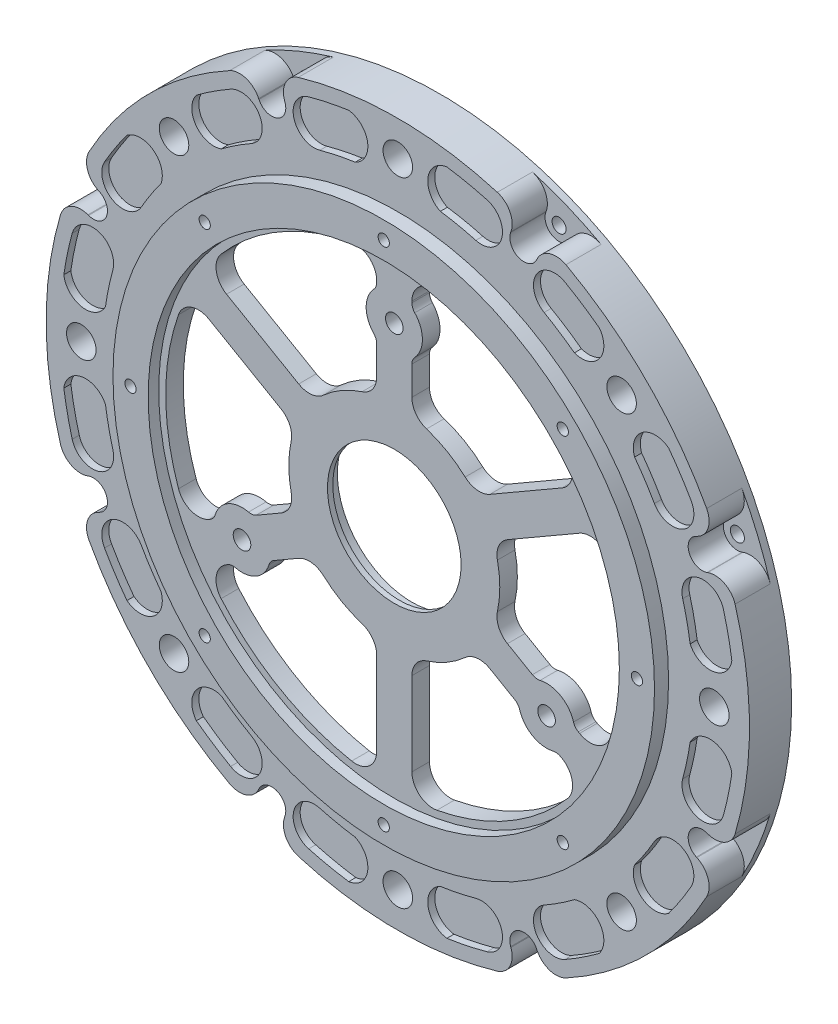
SolidWorks part; units mm, degrees
material "6061 Alloy"
ref_plane "Front Plane" through (0, 0, 0) normal (0, 0, 1) x (1, 0, 0)
ref_plane "Top Plane" through (0, 0, 0) normal (0, 1, 0) x (1, 0, 0)
ref_plane "Right Plane" through (0, 0, 0) normal (1, 0, 0) x (0, 0, -1)
sketch "Sketch1" plane through (0, 0, 0) normal (0, 0, 1) x (1, 0, 0)
  line L0 (0, 0) -> (0, 55.0351) construction
  line L1 (26.3498, 12.3263) -> (16.0929, 6.4045)
  line L2 (23.8498, 16.6564) -> (13.5929, 10.7346)
  line L3 (2.5, 28.9828) -> (2.5, 28.7749)
  line L4 (-2.5, 28.9828) -> (-2.5, 28.7749)
  line L5 (23.8498, -16.6564) -> (23.6698, -16.5525)
  line L6 (26.3498, -12.3263) -> (26.1698, -12.2224)
  line L7 (-2.5, -28.9828) -> (-2.5, -17.1391)
  line L8 (2.5, -28.9828) -> (2.5, -17.1391)
  line L9 (-26.3498, -12.3263) -> (-26.1698, -12.2224)
  line L10 (-23.8498, -16.6564) -> (-23.6698, -16.5525)
  line L11 (-23.8498, 16.6564) -> (-13.5929, 10.7346)
  line L12 (-26.3498, 12.3263) -> (-16.0929, 6.4045)
  line L13 (2.5, 21.2251) -> (2.5, 17.1391)
  line L14 (-2.5, 21.2251) -> (-2.5, 17.1391)
  line L15 (19.6315, -8.4475) -> (16.0929, -6.4045)
  line L16 (17.1315, -12.7776) -> (13.5929, -10.7346)
  line L17 (-17.1315, -12.7776) -> (-13.5929, -10.7346)
  line L18 (-19.6315, -8.4475) -> (-16.0929, -6.4045)
  circle A0 centre (0, 0) radius 50
  arc A3 (-6.0593, 31.9302) -> (-24.6227, 21.2126) centre (0, 0) ccw
  arc A4 (-4.5833, 14.2826) -> (-10.0774, 11.1106) centre (0, 0) ccw
  arc A5 (-6.0593, 31.9302) -> (-2.5, 28.9828) centre (-5.5, 28.9828) cw
  arc A6 (-4.5833, 14.2826) -> (-2.5, 17.1391) centre (-5.5, 17.1391) ccw
  arc A7 (2.5, 17.1391) -> (4.5833, 14.2826) centre (5.5, 17.1391) ccw
  arc A8 (6.0593, 31.9302) -> (2.5, 28.9828) centre (5.5, 28.9828) ccw
  arc A9 (30.682, 10.7175) -> (26.3498, 12.3263) centre (27.8498, 9.7282) ccw
  arc A10 (16.0929, 6.4045) -> (14.6608, 3.172) centre (17.5929, 3.8064) ccw
  arc A11 (10.0774, 11.1106) -> (13.5929, 10.7346) centre (12.0929, 13.3327) ccw
  arc A12 (24.6227, 21.2126) -> (23.8498, 16.6564) centre (22.3498, 19.2545) cw
  arc A13 (24.6227, -21.2126) -> (23.8498, -16.6564) centre (22.3498, -19.2545) ccw
  arc A14 (13.5929, -10.7346) -> (10.0774, -11.1106) centre (12.0929, -13.3327) ccw
  arc A15 (14.6608, -3.172) -> (16.0929, -6.4045) centre (17.5929, -3.8064) ccw
  arc A16 (30.682, -10.7175) -> (26.3498, -12.3263) centre (27.8498, -9.7282) cw
  arc A17 (-6.0593, -31.9302) -> (-2.5, -28.9828) centre (-5.5, -28.9828) ccw
  arc A18 (-2.5, -17.1391) -> (-4.5833, -14.2826) centre (-5.5, -17.1391) ccw
  arc A19 (4.5833, -14.2826) -> (2.5, -17.1391) centre (5.5, -17.1391) ccw
  arc A20 (6.0593, -31.9302) -> (2.5, -28.9828) centre (5.5, -28.9828) cw
  arc A21 (-30.682, -10.7175) -> (-26.3498, -12.3263) centre (-27.8498, -9.7282) ccw
  arc A22 (-16.0929, -6.4045) -> (-14.6608, -3.172) centre (-17.5929, -3.8064) ccw
  arc A23 (-10.0774, -11.1106) -> (-13.5929, -10.7346) centre (-12.0929, -13.3327) ccw
  arc A24 (-24.6227, -21.2126) -> (-23.8498, -16.6564) centre (-22.3498, -19.2545) cw
  arc A25 (-24.6227, 21.2126) -> (-23.8498, 16.6564) centre (-22.3498, 19.2545) ccw
  arc A26 (-13.5929, 10.7346) -> (-10.0774, 11.1106) centre (-12.0929, 13.3327) ccw
  arc A27 (-14.6608, 3.172) -> (-16.0929, 6.4045) centre (-17.5929, 3.8064) ccw
  arc A28 (-30.682, 10.7175) -> (-26.3498, 12.3263) centre (-27.8498, 9.7282) cw
  arc A29 (-30.682, 10.7175) -> (-30.682, -10.7175) centre (0, 0) ccw
  arc A30 (-24.6227, -21.2126) -> (-6.0593, -31.9302) centre (0, 0) ccw
  arc A31 (6.0593, -31.9302) -> (24.6227, -21.2126) centre (0, 0) ccw
  arc A32 (30.682, -10.7175) -> (30.682, 10.7175) centre (0, 0) ccw
  arc A33 (24.6227, 21.2126) -> (6.0593, 31.9302) centre (0, 0) ccw
  arc A34 (-14.6608, 3.172) -> (-14.6608, -3.172) centre (0, 0) ccw
  arc A35 (-10.0774, -11.1106) -> (-4.5833, -14.2826) centre (0, 0) ccw
  arc A36 (4.5833, -14.2826) -> (10.0774, -11.1106) centre (0, 0) ccw
  arc A37 (14.6608, -3.172) -> (14.6608, 3.172) centre (0, 0) ccw
  arc A38 (10.0774, 11.1106) -> (4.5833, 14.2826) centre (0, 0) ccw
  circle A39 centre (0, 0) radius 10.6
  circle A40 centre (0, 0) radius 25 construction
  arc A41 (2.9091, 22.2546) -> (2.9091, 27.7454) centre (0, 25) ccw
  arc A42 (-2.9091, 27.7454) -> (-2.9091, 22.2546) centre (0, 25) ccw
  arc A43 (17.8185, -13.6466) -> (22.5737, -16.392) centre (21.6506, -12.5) ccw
  arc A44 (25.4828, -11.3534) -> (20.7276, -8.608) centre (21.6506, -12.5) ccw
  arc A45 (-20.7276, -8.608) -> (-25.4828, -11.3534) centre (-21.6506, -12.5) ccw
  arc A46 (-22.5737, -16.392) -> (-17.8185, -13.6466) centre (-21.6506, -12.5) ccw
  arc A47 (17.8185, -13.6466) -> (17.1315, -12.7776) centre (16.3815, -14.0766) ccw
  arc A48 (19.6315, -8.4475) -> (20.7276, -8.608) centre (20.3815, -7.1484) ccw
  arc A49 (25.4828, -11.3534) -> (26.1698, -12.2224) centre (26.9198, -10.9234) ccw
  arc A50 (22.5737, -16.392) -> (23.6698, -16.5525) centre (22.9198, -17.8516) cw
  arc A51 (-25.4828, -11.3534) -> (-26.1698, -12.2224) centre (-26.9198, -10.9234) cw
  arc A52 (-22.5737, -16.392) -> (-23.6698, -16.5525) centre (-22.9198, -17.8516) ccw
  arc A53 (-17.8185, -13.6466) -> (-17.1315, -12.7776) centre (-16.3815, -14.0766) cw
  arc A54 (-19.6315, -8.4475) -> (-20.7276, -8.608) centre (-20.3815, -7.1484) cw
  arc A55 (2.5, 21.2251) -> (2.9091, 22.2546) centre (4, 21.2251) cw
  arc A56 (2.9091, 27.7454) -> (2.5, 28.7749) centre (4, 28.7749) cw
  arc A57 (-2.9091, 22.2546) -> (-2.5, 21.2251) centre (-4, 21.2251) cw
  arc A58 (-2.5, 28.7749) -> (-2.9091, 27.7454) centre (-4, 28.7749) cw
  point P82 (0, 0)
  point P97 (0, 0)
  point P119 (-2.5, 28.1225)
  dimension "D1" = 100
  dimension "D2" = 21.2
  dimension "D5" = 50
  dimension "D6" = 65
  dimension "D7" = 30
  dimension "D8" = 3
  dimension "D10" = 8
  dimension "D12" = 1.5
  dimension "D3" = 2.5
  dimension "D4" = 2.5
  dimension "D9" = 6
  dimension "D11" = 3
extrude "Boss-Extrude1" add sketch "Sketch1" along normal blind 9
sketch "Sketch2" plane through (0, 0, 0) normal (0, 0, 1) x (1, 0, 0)
  line L17 (-3.8971, 42.75) -> (-5.0043, 44.6677)
  line L56 (19.6941, 40.983) -> (19.9564, 41.1843)
  line L57 (3.8971, 42.75) -> (5.0043, 44.6677)
  line L58 (40.983, 19.6941) -> (41.1843, 19.9564)
  line L59 (27.4731, 32.9845) -> (28.0463, 35.1234)
  line L60 (42.9052, 15.0535) -> (43.233, 15.0104)
  line L61 (32.9845, 27.4731) -> (35.1234, 28.0463)
  line L62 (42.9052, -15.0535) -> (43.233, -15.0104)
  line L63 (42.75, 3.8971) -> (44.6677, 5.0043)
  line L64 (40.983, -19.6941) -> (41.1843, -19.9564)
  line L65 (42.75, -3.8971) -> (44.6677, -5.0043)
  line L66 (19.6941, -40.983) -> (19.9564, -41.1843)
  line L67 (32.9845, -27.4731) -> (35.1234, -28.0463)
  line L68 (15.0535, -42.9052) -> (15.0104, -43.233)
  line L69 (27.4731, -32.9845) -> (28.0463, -35.1234)
  line L70 (-15.0535, -42.9052) -> (-15.0104, -43.233)
  line L71 (3.8971, -42.75) -> (5.0043, -44.6677)
  line L72 (-19.6941, -40.983) -> (-19.9564, -41.1843)
  line L73 (-3.8971, -42.75) -> (-5.0043, -44.6677)
  line L74 (-40.983, -19.6941) -> (-41.1843, -19.9564)
  line L75 (-27.4731, -32.9845) -> (-28.0463, -35.1234)
  line L76 (0, 0) -> (0, 52.4279) construction
  line L77 (0, 0) -> (17.9287, 43.2838) construction
  line L78 (-42.9052, -15.0535) -> (-43.233, -15.0104)
  line L79 (-32.9845, -27.4731) -> (-35.1234, -28.0463)
  line L80 (-42.9052, 15.0535) -> (-43.233, 15.0104)
  line L81 (-42.75, -3.8971) -> (-44.6677, -5.0043)
  line L82 (-40.983, 19.6941) -> (-41.1843, 19.9564)
  line L83 (-42.75, 3.8971) -> (-44.6677, 5.0043)
  line L84 (-19.6941, 40.983) -> (-19.9564, 41.1843)
  line L85 (-32.9845, 27.4731) -> (-35.1234, 28.0463)
  line L86 (-15.0535, 42.9052) -> (-15.0104, 43.233)
  line L87 (-27.4731, 32.9845) -> (-28.0463, 35.1234)
  line L88 (15.0535, 42.9052) -> (15.0104, 43.233)
  arc A46 (-3.8971, 42.75) -> (3.8971, 42.75) centre (0, 45) ccw
  arc A110 (15.0535, 42.9052) -> (19.6941, 40.983) centre (17.9287, 43.2838) ccw
  circle A111 centre (0, 0) radius 46.85 construction
  circle A112 centre (0, 0) radius 45 construction
  arc A114 (19.9564, 41.1843) -> (23.2512, 41.4202) centre (21.7827, 38.8042) cw
  arc A115 (5.0043, 44.6677) -> (9.2471, 46.5912) centre (8.4684, 42.6677) cw
  arc A116 (15.0104, 43.233) -> (12.8475, 45.7296) centre (12.036, 42.8414) ccw
  arc A117 (-5.0043, 44.6677) -> (-9.2471, 46.5912) centre (-8.4684, 42.6677) ccw
  arc A118 (27.4731, 32.9845) -> (32.9845, 27.4731) centre (31.8198, 31.8198) ccw
  arc A119 (40.983, 19.6941) -> (42.9052, 15.0535) centre (43.2838, 17.9287) ccw
  arc A120 (43.233, 15.0104) -> (45.7296, 12.8475) centre (42.8414, 12.036) cw
  arc A121 (35.1234, 28.0463) -> (39.4837, 26.4063) centre (36.1587, 24.1826) cw
  arc A122 (41.1843, 19.9564) -> (41.4202, 23.2512) centre (38.8042, 21.7827) ccw
  arc A123 (28.0463, 35.1234) -> (26.4063, 39.4837) centre (24.1826, 36.1587) ccw
  arc A124 (42.75, 3.8971) -> (42.75, -3.8971) centre (45, 0) ccw
  arc A125 (42.9052, -15.0535) -> (40.983, -19.6941) centre (43.2838, -17.9287) ccw
  arc A126 (41.1843, -19.9564) -> (41.4202, -23.2512) centre (38.8042, -21.7827) cw
  arc A127 (44.6677, -5.0043) -> (46.5912, -9.2471) centre (42.6677, -8.4684) cw
  arc A128 (43.233, -15.0104) -> (45.7296, -12.8475) centre (42.8414, -12.036) ccw
  arc A129 (44.6677, 5.0043) -> (46.5912, 9.2471) centre (42.6677, 8.4684) ccw
  arc A130 (32.9845, -27.4731) -> (27.4731, -32.9845) centre (31.8198, -31.8198) ccw
  arc A131 (19.6941, -40.983) -> (15.0535, -42.9052) centre (17.9287, -43.2838) ccw
  arc A132 (15.0104, -43.233) -> (12.8475, -45.7296) centre (12.036, -42.8414) cw
  arc A133 (28.0463, -35.1234) -> (26.4063, -39.4837) centre (24.1826, -36.1587) cw
  arc A134 (19.9564, -41.1843) -> (23.2512, -41.4202) centre (21.7827, -38.8042) ccw
  arc A135 (35.1234, -28.0463) -> (39.4837, -26.4063) centre (36.1587, -24.1826) ccw
  arc A136 (3.8971, -42.75) -> (-3.8971, -42.75) centre (0, -45) ccw
  arc A137 (-15.0535, -42.9052) -> (-19.6941, -40.983) centre (-17.9287, -43.2838) ccw
  arc A138 (-19.9564, -41.1843) -> (-23.2512, -41.4202) centre (-21.7827, -38.8042) cw
  arc A139 (-5.0043, -44.6677) -> (-9.2471, -46.5912) centre (-8.4684, -42.6677) cw
  arc A140 (-15.0104, -43.233) -> (-12.8475, -45.7296) centre (-12.036, -42.8414) ccw
  arc A141 (5.0043, -44.6677) -> (9.2471, -46.5912) centre (8.4684, -42.6677) ccw
  arc A142 (-27.4731, -32.9845) -> (-32.9845, -27.4731) centre (-31.8198, -31.8198) ccw
  arc A143 (-40.983, -19.6941) -> (-42.9052, -15.0535) centre (-43.2838, -17.9287) ccw
  arc A144 (-43.233, -15.0104) -> (-45.7296, -12.8475) centre (-42.8414, -12.036) cw
  arc A145 (-35.1234, -28.0463) -> (-39.4837, -26.4063) centre (-36.1587, -24.1826) cw
  arc A146 (-41.1843, -19.9564) -> (-41.4202, -23.2512) centre (-38.8042, -21.7827) ccw
  arc A147 (-28.0463, -35.1234) -> (-26.4063, -39.4837) centre (-24.1826, -36.1587) ccw
  arc A148 (-42.75, -3.8971) -> (-42.75, 3.8971) centre (-45, 0) ccw
  arc A149 (-42.9052, 15.0535) -> (-40.983, 19.6941) centre (-43.2838, 17.9287) ccw
  arc A150 (-41.1843, 19.9564) -> (-41.4202, 23.2512) centre (-38.8042, 21.7827) cw
  arc A151 (-44.6677, 5.0043) -> (-46.5912, 9.2471) centre (-42.6677, 8.4684) cw
  arc A152 (-43.233, 15.0104) -> (-45.7296, 12.8475) centre (-42.8414, 12.036) ccw
  arc A153 (-44.6677, -5.0043) -> (-46.5912, -9.2471) centre (-42.6677, -8.4684) ccw
  arc A154 (-32.9845, 27.4731) -> (-27.4731, 32.9845) centre (-31.8198, 31.8198) ccw
  arc A155 (-19.6941, 40.983) -> (-15.0535, 42.9052) centre (-17.9287, 43.2838) ccw
  arc A156 (-15.0104, 43.233) -> (-12.8475, 45.7296) centre (-12.036, 42.8414) cw
  arc A157 (-28.0463, 35.1234) -> (-26.4063, 39.4837) centre (-24.1826, 36.1587) cw
  arc A158 (-19.9564, 41.1843) -> (-23.2512, 41.4202) centre (-21.7827, 38.8042) ccw
  arc A159 (-35.1234, 28.0463) -> (-39.4837, 26.4063) centre (-36.1587, 24.1826) ccw
  arc A160 (26.4063, 39.4837) -> (23.2512, 41.4202) centre (0, 0) ccw
  arc A161 (12.8475, 45.7296) -> (9.2471, 46.5912) centre (0, 0) ccw
  arc A162 (-9.2471, 46.5912) -> (-12.8475, 45.7296) centre (0, 0) ccw
  arc A163 (-23.2512, 41.4202) -> (-26.4063, 39.4837) centre (0, 0) ccw
  arc A164 (-39.4837, 26.4063) -> (-41.4202, 23.2512) centre (0, 0) ccw
  arc A165 (-45.7296, 12.8475) -> (-46.5912, 9.2471) centre (0, 0) ccw
  arc A166 (-46.5912, -9.2471) -> (-45.7296, -12.8475) centre (0, 0) ccw
  arc A167 (-41.4202, -23.2512) -> (-39.4837, -26.4063) centre (0, 0) ccw
  arc A168 (-26.4063, -39.4837) -> (-23.2512, -41.4202) centre (0, 0) ccw
  arc A169 (-12.8475, -45.7296) -> (-9.2471, -46.5912) centre (0, 0) ccw
  arc A170 (9.2471, -46.5912) -> (12.8475, -45.7296) centre (0, 0) ccw
  arc A171 (23.2512, -41.4202) -> (26.4063, -39.4837) centre (0, 0) ccw
  arc A172 (39.4837, -26.4063) -> (41.4202, -23.2512) centre (0, 0) ccw
  arc A173 (45.7296, -12.8475) -> (46.5912, -9.2471) centre (0, 0) ccw
  arc A174 (46.5912, 9.2471) -> (45.7296, 12.8475) centre (0, 0) ccw
  arc A175 (41.4202, 23.2512) -> (39.4837, 26.4063) centre (0, 0) ccw
  point P159 (0, 0)
  dimension "D1" = 2.9
  dimension "D2" = 93.7
  dimension "D3" = 90
  dimension "D4" = 22.5
  dimension "D5" = 95
  dimension "D6" = 9
  dimension "D9" = 3
  dimension "D10" = 4
  dimension "D7" = 8
extrude "Cut-Extrude2" cut sketch "Sketch2" along normal blind 5 from surface starting at face at (-14.1218, -17.8169, 0)
sketch "Sketch3" plane through (0, 0, 0) normal (0, 0, 1) x (1, 0, 0)
  circle A0 centre (0, 0) radius 50
  circle A1 centre (0, 0) radius 48.4
  dimension "D1" = 100
  dimension "D2" = 96.8
extrude "Cut-Extrude3" cut sketch "Sketch3" along normal blind 1 from surface starting at face at (50, 0, 0)
sketch "Sketch4" plane through (0, 0, 0) normal (0, 0, 1) x (1, 0, 0)
  line L0 (0, 0) -> (0, 58.9666) construction
  line L1 (0, 0) -> (-11.6574, 58.6055) construction
  circle A0 centre (0, 0) radius 45 construction
  arc A3 (-12.6755, 46.2961) -> (-11.0911, 40.5091) centre (-11.8833, 43.4026) ccw
  arc A5 (-6.9776, 47.4901) -> (-12.6755, 46.2961) centre (0, 0) ccw
  arc A6 (-6.0511, 41.5618) -> (-11.0911, 40.5091) centre (0, 0) ccw
  arc A7 (-6.0511, 41.5618) -> (-6.9776, 47.4901) centre (-7.3833, 44.3902) ccw
  arc A8 (6.0511, 41.5618) -> (11.0911, 40.5091) centre (0, 0) cw
  arc A9 (6.0511, 41.5618) -> (6.9776, 47.4901) centre (7.3833, 44.3902) cw
  arc A10 (6.9776, 47.4901) -> (12.6755, 46.2961) centre (0, 0) cw
  arc A11 (12.6755, 46.2961) -> (11.0911, 40.5091) centre (11.8833, 43.4026) cw
  arc A12 (25.1099, 33.6674) -> (20.8017, 36.4868) centre (0, 0) ccw
  arc A13 (23.7733, 41.6993) -> (20.8017, 36.4868) centre (22.2875, 39.0931) ccw
  arc A14 (28.6467, 38.5145) -> (23.7733, 41.6993) centre (0, 0) ccw
  arc A15 (25.1099, 33.6674) -> (28.6467, 38.5145) centre (26.1678, 36.6094) ccw
  arc A16 (33.6674, 25.1099) -> (36.4868, 20.8017) centre (0, 0) cw
  arc A17 (33.6674, 25.1099) -> (38.5145, 28.6467) centre (36.6094, 26.1678) cw
  arc A18 (38.5145, 28.6467) -> (41.6993, 23.7733) centre (0, 0) cw
  arc A19 (41.6993, 23.7733) -> (36.4868, 20.8017) centre (39.0931, 22.2875) cw
  arc A20 (41.5618, 6.0511) -> (40.5091, 11.0911) centre (0, 0) ccw
  arc A21 (46.2961, 12.6755) -> (40.5091, 11.0911) centre (43.4026, 11.8833) ccw
  arc A22 (47.4901, 6.9776) -> (46.2961, 12.6755) centre (0, 0) ccw
  arc A23 (41.5618, 6.0511) -> (47.4901, 6.9776) centre (44.3902, 7.3833) ccw
  arc A24 (41.5618, -6.0511) -> (40.5091, -11.0911) centre (0, 0) cw
  arc A25 (41.5618, -6.0511) -> (47.4901, -6.9776) centre (44.3902, -7.3833) cw
  arc A26 (47.4901, -6.9776) -> (46.2961, -12.6755) centre (0, 0) cw
  arc A27 (46.2961, -12.6755) -> (40.5091, -11.0911) centre (43.4026, -11.8833) cw
  arc A28 (33.6674, -25.1099) -> (36.4868, -20.8017) centre (0, 0) ccw
  arc A29 (41.6993, -23.7733) -> (36.4868, -20.8017) centre (39.0931, -22.2875) ccw
  arc A30 (38.5145, -28.6467) -> (41.6993, -23.7733) centre (0, 0) ccw
  arc A31 (33.6674, -25.1099) -> (38.5145, -28.6467) centre (36.6094, -26.1678) ccw
  arc A32 (25.1099, -33.6674) -> (20.8017, -36.4868) centre (0, 0) cw
  arc A33 (25.1099, -33.6674) -> (28.6467, -38.5145) centre (26.1678, -36.6094) cw
  arc A34 (28.6467, -38.5145) -> (23.7733, -41.6993) centre (0, 0) cw
  arc A35 (23.7733, -41.6993) -> (20.8017, -36.4868) centre (22.2875, -39.0931) cw
  arc A36 (6.0511, -41.5618) -> (11.0911, -40.5091) centre (0, 0) ccw
  arc A37 (12.6755, -46.2961) -> (11.0911, -40.5091) centre (11.8833, -43.4026) ccw
  arc A38 (6.9776, -47.4901) -> (12.6755, -46.2961) centre (0, 0) ccw
  arc A39 (6.0511, -41.5618) -> (6.9776, -47.4901) centre (7.3833, -44.3902) ccw
  arc A40 (-6.0511, -41.5618) -> (-11.0911, -40.5091) centre (0, 0) cw
  arc A41 (-6.0511, -41.5618) -> (-6.9776, -47.4901) centre (-7.3833, -44.3902) cw
  arc A42 (-6.9776, -47.4901) -> (-12.6755, -46.2961) centre (0, 0) cw
  arc A43 (-12.6755, -46.2961) -> (-11.0911, -40.5091) centre (-11.8833, -43.4026) cw
  arc A44 (-25.1099, -33.6674) -> (-20.8017, -36.4868) centre (0, 0) ccw
  arc A45 (-23.7733, -41.6993) -> (-20.8017, -36.4868) centre (-22.2875, -39.0931) ccw
  arc A46 (-28.6467, -38.5145) -> (-23.7733, -41.6993) centre (0, 0) ccw
  arc A47 (-25.1099, -33.6674) -> (-28.6467, -38.5145) centre (-26.1678, -36.6094) ccw
  arc A48 (-33.6674, -25.1099) -> (-36.4868, -20.8017) centre (0, 0) cw
  arc A49 (-33.6674, -25.1099) -> (-38.5145, -28.6467) centre (-36.6094, -26.1678) cw
  arc A50 (-38.5145, -28.6467) -> (-41.6993, -23.7733) centre (0, 0) cw
  arc A51 (-41.6993, -23.7733) -> (-36.4868, -20.8017) centre (-39.0931, -22.2875) cw
  arc A52 (-41.5618, -6.0511) -> (-40.5091, -11.0911) centre (0, 0) ccw
  arc A53 (-46.2961, -12.6755) -> (-40.5091, -11.0911) centre (-43.4026, -11.8833) ccw
  arc A54 (-47.4901, -6.9776) -> (-46.2961, -12.6755) centre (0, 0) ccw
  arc A55 (-41.5618, -6.0511) -> (-47.4901, -6.9776) centre (-44.3902, -7.3833) ccw
  arc A56 (-41.5618, 6.0511) -> (-40.5091, 11.0911) centre (0, 0) cw
  arc A57 (-41.5618, 6.0511) -> (-47.4901, 6.9776) centre (-44.3902, 7.3833) cw
  arc A58 (-47.4901, 6.9776) -> (-46.2961, 12.6755) centre (0, 0) cw
  arc A59 (-46.2961, 12.6755) -> (-40.5091, 11.0911) centre (-43.4026, 11.8833) cw
  arc A60 (-33.6674, 25.1099) -> (-36.4868, 20.8017) centre (0, 0) ccw
  arc A61 (-41.6993, 23.7733) -> (-36.4868, 20.8017) centre (-39.0931, 22.2875) ccw
  arc A62 (-38.5145, 28.6467) -> (-41.6993, 23.7733) centre (0, 0) ccw
  arc A63 (-33.6674, 25.1099) -> (-38.5145, 28.6467) centre (-36.6094, 26.1678) ccw
  arc A64 (-25.1099, 33.6674) -> (-20.8017, 36.4868) centre (0, 0) cw
  arc A65 (-25.1099, 33.6674) -> (-28.6467, 38.5145) centre (-26.1678, 36.6094) cw
  arc A66 (-28.6467, 38.5145) -> (-23.7733, 41.6993) centre (0, 0) cw
  arc A67 (-23.7733, 41.6993) -> (-20.8017, 36.4868) centre (-22.2875, 39.0931) cw
  point P110 (0, 0)
  dimension "D2" = 90
  dimension "D5" = 6
  dimension "D6" = 8
  dimension "D8" = 96
  dimension "D9" = 84
  dimension "D1" = 11.25
  dimension "D7" = 4.5
extrude "Cut-Extrude4" cut sketch "Sketch4" against normal blind 3 from surface starting at face at (-8.369, 21.1383, 9)
sketch "Sketch5" plane through (0, 0, 0) normal (0, 0, 1) x (1, 0, 0)
  circle A0 centre (0, 0) radius 38.5
  circle A1 centre (0, 0) radius 33.5
  dimension "D1" = 67
  dimension "D2" = 77
sketch "Sketch6" plane through (0, 0, 0) normal (0, 0, 1) x (1, 0, 0)
  circle A0 centre (0, 0) radius 38.5
  circle A1 centre (0, 0) radius 50
  dimension "D1" = 100
  dimension "D2" = 77
extrude "Cut-Extrude5" cut sketch "Sketch6" against normal blind 2 from surface starting at face at (-8.369, 21.1383, 9)
extrude "Cut-Extrude6" cut sketch "Sketch5" against normal blind 1.5 from surface contours A1 region at (0, 0, 0) starting at face at (-22.4908, -3.3214, 9)
sketch "Sketch7" plane through (0, 0, 0) normal (0, 0, 1) x (1, 0, 0)
  circle A0 centre (0, 25) radius 1.5
  circle A2 centre (21.6506, -12.5) radius 1.5
  circle A3 centre (-21.6506, -12.5) radius 1.5
  circle A4 centre (0, 0) radius 36 construction
  circle A5 centre (0, 36) radius 1
  circle A6 centre (25.4558, 25.4558) radius 1
  circle A7 centre (36, 0) radius 1
  circle A8 centre (25.4558, -25.4558) radius 1
  circle A9 centre (0, -36) radius 1
  circle A10 centre (-25.4558, -25.4558) radius 1
  circle A11 centre (-36, 0) radius 1
  circle A12 centre (-25.4558, 25.4558) radius 1
  point P9 (0, 0)
  point P30 (0, 0)
  dimension "D1" = 3
  dimension "D3" = 72
  dimension "D4" = 2
  dimension "D2" = 3
  dimension "D5" = 8
sketch "Sketch16" plane through (0, 0, 0) normal (0, 0, 1) x (1, 0, 0)
  line L0 (0, 0) -> (0, 60.4181) construction
  circle A0 centre (0, 0) radius 45 construction
  circle A1 centre (0, 45) radius 2.5
  circle A2 centre (31.8198, 31.8198) radius 2.5
  circle A3 centre (45, 0) radius 2.5
  circle A4 centre (31.8198, -31.8198) radius 2.5
  circle A5 centre (0, -45) radius 2.5
  circle A6 centre (-31.8198, -31.8198) radius 2.5
  circle A7 centre (-45, 0) radius 2.5
  circle A8 centre (-31.8198, 31.8198) radius 2.5
  point P23 (0, 0)
  dimension "D1" = 90
  dimension "D2" = 5
  dimension "D3" = 8
sketch "Sketch22" plane through (0, 0, 0) normal (0, 0, 1) x (1, 0, 0)
  line L0 (0, 0) -> (-20.8165, 50.2555) construction
  line L1 (0, 0) -> (0, 52.0381) construction
  circle A0 centre (0, 0) radius 46.85 construction
  circle A1 centre (-17.9287, 43.2838) radius 1
  circle A3 centre (17.9287, 43.2838) radius 1
  circle A4 centre (43.2838, 17.9287) radius 1
  circle A5 centre (43.2838, -17.9287) radius 1
  circle A6 centre (17.9287, -43.2838) radius 1
  circle A7 centre (-17.9287, -43.2838) radius 1
  circle A8 centre (-43.2838, -17.9287) radius 1
  circle A9 centre (-43.2838, 17.9287) radius 1
  point P23 (0, 0)
  dimension "D1" = 93.7
  dimension "D3" = 2
  dimension "D4" = 8
  dimension "D2" = 22.5
extrude "Cut-Extrude9" cut sketch "Sketch22" against normal through all from surface contours A1 | A3 | A4 | A5 | A6 | A7 | A8 | A9 starting at face at (-9.3758, 43.8939, 7)
sketch "Sketch23" plane through (0, 0, 0) normal (0, 0, 1) x (1, 0, 0)
  line L0 (0, 0) -> (-20.6937, 49.959) construction
  line L1 (0, 0) -> (0, 52.176) construction
  line L4 (-19.7428, 42.4416) -> (-19.7821, 42.5262)
  line L5 (-16.0505, 43.971) -> (-16.0826, 44.0586)
  line L6 (16.0505, 43.971) -> (16.0826, 44.0586)
  line L7 (19.7428, 42.4416) -> (19.7821, 42.5262)
  line L8 (42.4416, 19.7428) -> (42.5262, 19.7821)
  line L9 (43.971, 16.0505) -> (44.0586, 16.0826)
  line L10 (43.971, -16.0505) -> (44.0586, -16.0826)
  line L11 (42.4416, -19.7428) -> (42.5262, -19.7821)
  line L12 (19.7428, -42.4416) -> (19.7821, -42.5262)
  line L13 (16.0505, -43.971) -> (16.0826, -44.0586)
  line L14 (-16.0505, -43.971) -> (-16.0826, -44.0586)
  line L15 (-19.7428, -42.4416) -> (-19.7821, -42.5262)
  line L16 (-42.4416, -19.7428) -> (-42.5262, -19.7821)
  line L17 (-43.971, -16.0505) -> (-44.0586, -16.0826)
  line L18 (-43.971, 16.0505) -> (-44.0586, 16.0826)
  line L19 (-42.4416, 19.7428) -> (-42.5262, 19.7821)
  circle A0 centre (0, 0) radius 46.85 construction
  arc A1 (-19.7428, 42.4416) -> (-16.0505, 43.971) centre (-17.9287, 43.2838) ccw
  arc A8 (-14.148, 47.9566) -> (-16.0826, 44.0586) centre (-13.2652, 45.0894) ccw
  arc A9 (-19.7821, 42.5262) -> (-23.9063, 43.9146) centre (-22.5031, 41.2629) ccw
  arc A10 (-14.148, 47.9566) -> (-23.9063, 43.9146) centre (0, 0) ccw
  arc A11 (16.0505, 43.971) -> (19.7428, 42.4416) centre (17.9287, 43.2838) ccw
  arc A12 (23.9063, 43.9146) -> (19.7821, 42.5262) centre (22.5031, 41.2629) ccw
  arc A13 (16.0826, 44.0586) -> (14.148, 47.9566) centre (13.2652, 45.0894) ccw
  arc A14 (23.9063, 43.9146) -> (14.148, 47.9566) centre (0, 0) ccw
  arc A15 (42.4416, 19.7428) -> (43.971, 16.0505) centre (43.2838, 17.9287) ccw
  arc A16 (47.9566, 14.148) -> (44.0586, 16.0826) centre (45.0894, 13.2652) ccw
  arc A17 (42.5262, 19.7821) -> (43.9146, 23.9063) centre (41.2629, 22.5031) ccw
  arc A18 (47.9566, 14.148) -> (43.9146, 23.9063) centre (0, 0) ccw
  arc A19 (43.971, -16.0505) -> (42.4416, -19.7428) centre (43.2838, -17.9287) ccw
  arc A20 (43.9146, -23.9063) -> (42.5262, -19.7821) centre (41.2629, -22.5031) ccw
  arc A21 (44.0586, -16.0826) -> (47.9566, -14.148) centre (45.0894, -13.2652) ccw
  arc A22 (43.9146, -23.9063) -> (47.9566, -14.148) centre (0, 0) ccw
  arc A23 (19.7428, -42.4416) -> (16.0505, -43.971) centre (17.9287, -43.2838) ccw
  arc A24 (14.148, -47.9566) -> (16.0826, -44.0586) centre (13.2652, -45.0894) ccw
  arc A25 (19.7821, -42.5262) -> (23.9063, -43.9146) centre (22.5031, -41.2629) ccw
  arc A26 (14.148, -47.9566) -> (23.9063, -43.9146) centre (0, 0) ccw
  arc A27 (-16.0505, -43.971) -> (-19.7428, -42.4416) centre (-17.9287, -43.2838) ccw
  arc A28 (-23.9063, -43.9146) -> (-19.7821, -42.5262) centre (-22.5031, -41.2629) ccw
  arc A29 (-16.0826, -44.0586) -> (-14.148, -47.9566) centre (-13.2652, -45.0894) ccw
  arc A30 (-23.9063, -43.9146) -> (-14.148, -47.9566) centre (0, 0) ccw
  arc A31 (-42.4416, -19.7428) -> (-43.971, -16.0505) centre (-43.2838, -17.9287) ccw
  arc A32 (-47.9566, -14.148) -> (-44.0586, -16.0826) centre (-45.0894, -13.2652) ccw
  arc A33 (-42.5262, -19.7821) -> (-43.9146, -23.9063) centre (-41.2629, -22.5031) ccw
  arc A34 (-47.9566, -14.148) -> (-43.9146, -23.9063) centre (0, 0) ccw
  arc A35 (-43.971, 16.0505) -> (-42.4416, 19.7428) centre (-43.2838, 17.9287) ccw
  arc A36 (-43.9146, 23.9063) -> (-42.5262, 19.7821) centre (-41.2629, 22.5031) ccw
  arc A37 (-44.0586, 16.0826) -> (-47.9566, 14.148) centre (-45.0894, 13.2652) ccw
  arc A38 (-43.9146, 23.9063) -> (-47.9566, 14.148) centre (0, 0) ccw
  point P79 (0, 0)
  point P96 (0, 0)
  dimension "D1" = 93.7
  dimension "D3" = 4
  dimension "D4" = 3
  dimension "D5" = 100
  dimension "D2" = 22.5
  dimension "D6" = 8
extrude "Cut-Extrude10" cut sketch "Sketch23" against normal blind 5 and the other way through all from surface contours A1 | L15 | A12 A14 A13 L6 A11 L7 | A20 A22 A21 L10 A19 L11 | A24 A26 A25 L12 A23 L13 | A36 A38 A37 L18 A35 L19 | A32 A34 A33 L16 A31 L17 | A28 A30 A29 L14 A27 L15 | A16 A18 A17 L8 A15 L9 region at (-18.3409, 44.2789, 0) region at (18.3409, 44.2789, 0) region at (44.2789, 18.3409, 0) region at (44.2789, -18.3409, 0) region at (18.3409, -44.2789, 0) region at (-18.3409, -44.2789, 0) region at (-44.2789, -18.3409, 0) region at (-44.2789, 18.3409, 0) starting at face at (-42.2838, 17.9287, 7)
sketch "Sketch26" plane through (0, 0, 0) normal (0, 0, 1) x (1, 0, 0)
  circle A0 centre (0, 0) radius 10.75
  circle A1 centre (0, 0) radius 9.5
  dimension "D1" = 21.5
  dimension "D2" = 19
extrude "Boss-Extrude3" add sketch "Sketch26" against normal blind 0.75 from surface starting at face at (-8.369, 21.1383, 7.5)
hole_wizard "M3 Tapped Hole2" positions "Sketch33" profile "Sketch34" tap size "M3" standard "ISO" end condition through all
sketch "Sketch33" plane through (0, 0, 7.5) normal (0, 0, 1) x (1, 0, 0)
  point P0 (0, 25)
  point P3 (-21.6506, -12.5)
  point P6 (21.6506, -12.5)
sketch "Sketch34" plane through (0, 25, 7.5) normal (1, 0, 0) x (0, -1, 0)
  line L0 (0, 0) -> (0, 7.5)
  line L1 (0, 7.5) -> (1.25, 7.5)
  line L2 (1.25, 7.5) -> (1.25, 0)
  line L5 (1.25, 0) -> (0, 0)
  line L11 (0, -6.35) -> (0, 107.95) construction
  dimension "Thru Tap Drill Dia." = 2.5
  dimension "Thru Tap Drill Depth" = 7.5
cosmetic thread "Hole Thread4" parameters "D2"=3
cosmetic thread "Hole Thread5" parameters "D2"=3
cosmetic thread "Hole Thread6" parameters "D2"=3
hole_wizard "M5 Tapped Hole1" positions "Sketch35" profile "Sketch37" tap size "M5" standard "ISO" end condition through all
sketch "Sketch35" plane through (0, 0, 7) normal (0, 0, 1) x (1, 0, 0)
  point P0 (0, 45)
  point P3 (-31.8198, 31.8198)
  point P6 (-45, 0)
  point P9 (-31.8198, -31.8198)
  point P12 (0, -45)
  point P15 (31.8198, -31.8198)
  point P18 (45, 0)
  point P21 (31.8198, 31.8198)
cosmetic thread "Hole Thread7" parameters "D2"=5
cosmetic thread "Hole Thread8" parameters "D2"=5
cosmetic thread "Hole Thread9" parameters "D2"=5
cosmetic thread "Hole Thread10" parameters "D2"=5
cosmetic thread "Hole Thread11" parameters "D2"=5
cosmetic thread "Hole Thread12" parameters "D2"=5
cosmetic thread "Hole Thread13" parameters "D2"=5
cosmetic thread "Hole Thread14" parameters "D2"=5
sketch "Sketch37" plane through (0, 45, 7) normal (1, 0, 0) x (0, -1, 0)
  line L0 (0, 0) -> (0, 7)
  line L1 (0, 7) -> (2.1, 7)
  line L2 (2.1, 7) -> (2.1, 0)
  line L5 (2.1, 0) -> (0, 0)
  line L11 (0, -6.35) -> (0, 107.95) construction
  dimension "Thru Tap Drill Dia." = 4.2
  dimension "Thru Tap Drill Depth" = 7
hole_wizard "M2 Tapped Hole1" positions "Sketch38" profile "Sketch39" tap size "M2" standard "ISO" end condition through all
sketch "Sketch38" plane through (0, 0, 9) normal (0, 0, 1) x (1, 0, 0)
  point P0 (0, 36)
  point P3 (-25.4558, 25.4558)
  point P6 (-36, 0)
  point P9 (-25.4558, -25.4558)
  point P12 (0, -36)
  point P15 (25.4558, -25.4558)
  point P18 (36, 0)
  point P21 (25.4558, 25.4558)
sketch "Sketch39" plane through (0, 36, 9) normal (1, 0, 0) x (0, -1, 0)
  line L0 (0, 0) -> (0, 9)
  line L1 (0, 9) -> (0.8, 9)
  line L2 (0.8, 9) -> (0.8, 0)
  line L5 (0.8, 0) -> (0, 0)
  line L11 (0, -6.35) -> (0, 107.95) construction
  dimension "Thru Tap Drill Dia." = 1.6
  dimension "Thru Tap Drill Depth" = 9
cosmetic thread "Hole Thread15" parameters "D2"=2
cosmetic thread "Hole Thread16" parameters "D2"=2
cosmetic thread "Hole Thread17" parameters "D2"=2
cosmetic thread "Hole Thread18" parameters "D2"=2
cosmetic thread "Hole Thread19" parameters "D2"=2
cosmetic thread "Hole Thread20" parameters "D2"=2
cosmetic thread "Hole Thread21" parameters "D2"=2
cosmetic thread "Hole Thread22" parameters "D2"=2
